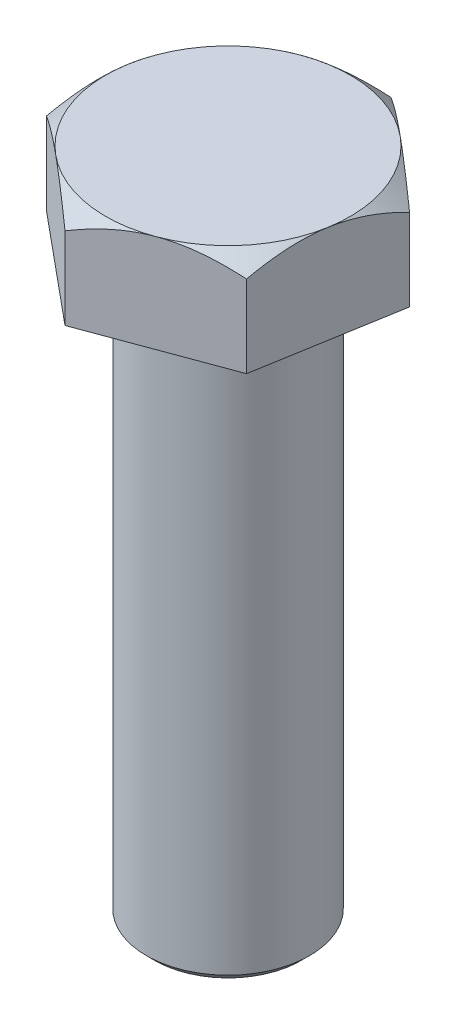
SolidWorks part; units mm, degrees
ref_plane "Front Plane" through (0, 0, 0) normal (0, 0, 1) x (1, 0, 0)
ref_plane "Top Plane" through (0, 0, 0) normal (0, 1, 0) x (1, 0, 0)
ref_plane "Right Plane" through (0, 0, 0) normal (1, 0, 0) x (0, 0, -1)
sketch "Sketch1" plane through (0, 0, 0) normal (0, 0, 1) x (1, 0, 0)
  line L1 (10, 70) -> (0, 70)
  line L2 (10, 70) -> (10, 0)
  line L3 (10, 0) -> (0, 0)
  line L4 (0, 70) -> (0, 0)
  line L5 (10, 70) -> (0, 0) construction
  line L6 (10, 0) -> (0, 70) construction
  point P0 (5, 35)
  dimension "D1" = 10
  dimension "D2" = 70
revolve "Revolve1" add sketch "Sketch1" angle 360 about L4
sketch "Sketch2" plane through (0, 70, 0) normal (0, 1, 0) x (1, 0, 0)
  line L1 (13.3315, -11.0577) -> (16.242, 6.0166)
  line L2 (16.242, 6.0166) -> (2.9105, 17.0742)
  line L3 (2.9105, 17.0742) -> (-13.3315, 11.0577)
  line L4 (-13.3315, 11.0577) -> (-16.242, -6.0166)
  line L5 (-16.242, -6.0166) -> (-2.9105, -17.0742)
  line L6 (-2.9105, -17.0742) -> (13.3315, -11.0577)
  circle A0 centre (0, 0) radius 15 construction
  dimension "D1" = 30
extrude "Boss-Extrude1" add sketch "Sketch2" along normal blind 12
sketch "Sketch3" plane through (0, 82, 0) normal (0, 1, 0) x (1, 0, 0)
  line L0 (16.242, 6.0166) -> (2.9105, 17.0742) construction
  circle A0 centre (0, 0) radius 15
extrude "Cut-Extrude1" cut sketch "Sketch3" against normal blind 3 draft 50 flip side to cut
ref_axis "Axis1" through (0, 0, 0) along (0, 1, 0)
chamfer "Chamfer1" distance 1 angle 45 1 edges at (-10, 0, 0)
